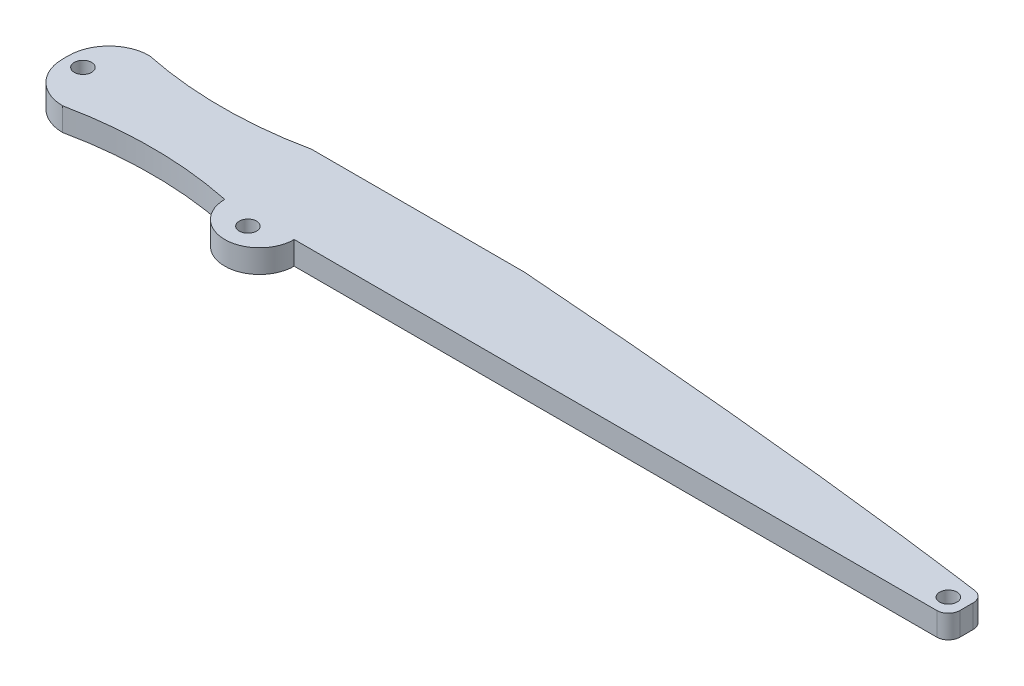
SolidWorks part; units mm, degrees
ref_plane "Front Plane" through (0, 0, 0) normal (0, 0, 1) x (1, 0, 0)
ref_plane "Top Plane" through (0, 0, 0) normal (0, 1, 0) x (1, 0, 0)
ref_plane "Right Plane" through (0, 0, 0) normal (1, 0, 0) x (0, 0, -1)
sketch "Sketch2" plane through (0, 0, 0) normal (0, 1, 0) x (1, 0, 0)
  line L11 (-80, 7.5) -> (80, 7.5)
  line L12 (-80, 7.5) -> (-80, -7.5)
  line L13 (-80, -7.5) -> (80, -7.5)
  line L14 (80, 7.5) -> (80, -7.5)
  dimension "D2" = 80
  dimension "D1" = 160
  dimension "D3" = 15
  dimension "D4" = 7.5
extrude "Boss-Extrude1" add sketch "Sketch2" along normal blind 4
sketch "Sketch4" plane through (0, 0, 0) normal (0, 1, 0) x (1, 0, 0)
  line L0 (-80, -7.5) -> (80, -7.5) construction
  line L1 (-45, -7.5) -> (-33, -7.5)
  arc A0 (-45, -7.5) -> (-33, -7.5) centre (-39, -7.5) ccw
  dimension "D1" = 6
  dimension "D2" = 35
  dimension "D3" = 12
extrude "Boss-Extrude2" add sketch "Sketch4" along normal up to surface (4 mm away) up to face at (0, 4, 0)
sketch "Sketch5" plane through (0, 4, 0) normal (0, 1, 0) x (1, 0, 0)
  line L0 (-80, -7.5) -> (-45, -7.5) construction
  line L1 (-80, 7.5) -> (-80, -7.5) construction
  line L2 (80, -7.5) -> (80, 7.5) construction
  line L3 (-33, -7.5) -> (80, -7.5) construction
  circle A0 centre (-77, 0) radius 1.5
  circle A1 centre (-39, -9.5) radius 1.5
  circle A2 centre (77, -4.5) radius 1.5
  arc A3 (-45, -7.5) -> (-33, -7.5) centre (-39, -7.5) ccw construction
  point P10 (-39, -13.5)
  dimension "D1" = 3
  dimension "D2" = 3
  dimension "D3" = 3
  dimension "D4" = 6
  dimension "D5" = 4
  dimension "D6" = 7.5
  dimension "D7" = 3
  dimension "D8" = 3
  dimension "D9" = 3
extrude "Cut-Extrude1" cut sketch "Sketch5" against normal through all
sketch "Sketch6" plane through (0, 4, 0) normal (0, 1, 0) x (1, 0, 0)
  line L2 (80, 7.5) -> (-8.2315, 7.5)
  line L3 (80, 7.5) -> (-80, 7.5) construction
  line L6 (-8.2315, 7.5) -> (14.2901, 5.8703) construction
  line L7 (14.2901, 5.8703) -> (49.5381, 2.8486) construction
  line L8 (49.5381, 2.8486) -> (69.508, -0.0694) construction
  line L9 (69.508, -0.0694) -> (80, -1.4494) construction
  line L10 (80, -7.5) -> (80, 7.5) construction
  line L11 (80, -1.4494) -> (80, 7.5)
  spline S0 degree 4 poles (-8.2315, 7.5) (14.2901, 5.8703) (49.5381, 2.8486) (69.508, -0.0694) (80, -1.4494) knots 0 0 0 0 0 1 1 1 1 1
  point P2 (0, 0)
  dimension "D1" = 88.6991
  dimension "D8" = 1.6297
  dimension "D2" = 88.2315
  dimension "D3" = 8.9494
  dimension "D4" = 10.5824
  dimension "D5" = 19.9699
  dimension "D6" = 22.5216
  dimension "D7" = 35.248
extrude "Cut-Extrude2" cut sketch "Sketch6" against normal through all
fillet "Fillet1" radius 7 2 edges at (-80, 2, -7.5) (-80, 2, 7.5)
fillet "Fillet2" radius 2 3 edges at (-8.2315, 2, -7.5) (80, 2, 7.5) (80, 2, 1.4494)
sketch "Sketch7" plane through (0, 4, 0) normal (0, 1, 0) x (1, 0, 0)
  line L0 (-73, -7.5) -> (-45, -7.5)
  line L1 (-73, -7.5) -> (-45, -7.5) construction
  line L2 (-73, 7.5) -> (-45, 7.5)
  line L3 (-8.3038, 7.5) -> (-73, 7.5) construction
  arc A1 (-45, -7.5) -> (-73, -7.5) centre (-59, -74.1454) ccw
  arc A2 (-73, 7.5) -> (-45, 7.5) centre (-59, 74.1454) ccw
  point P9 (-73, 7.5)
  point P10 (-45, 7.5)
  dimension "D1" = 68.1
  dimension "D2" = 28
  dimension "D3" = 68.1
extrude "Cut-Extrude3" cut sketch "Sketch7" against normal through all
